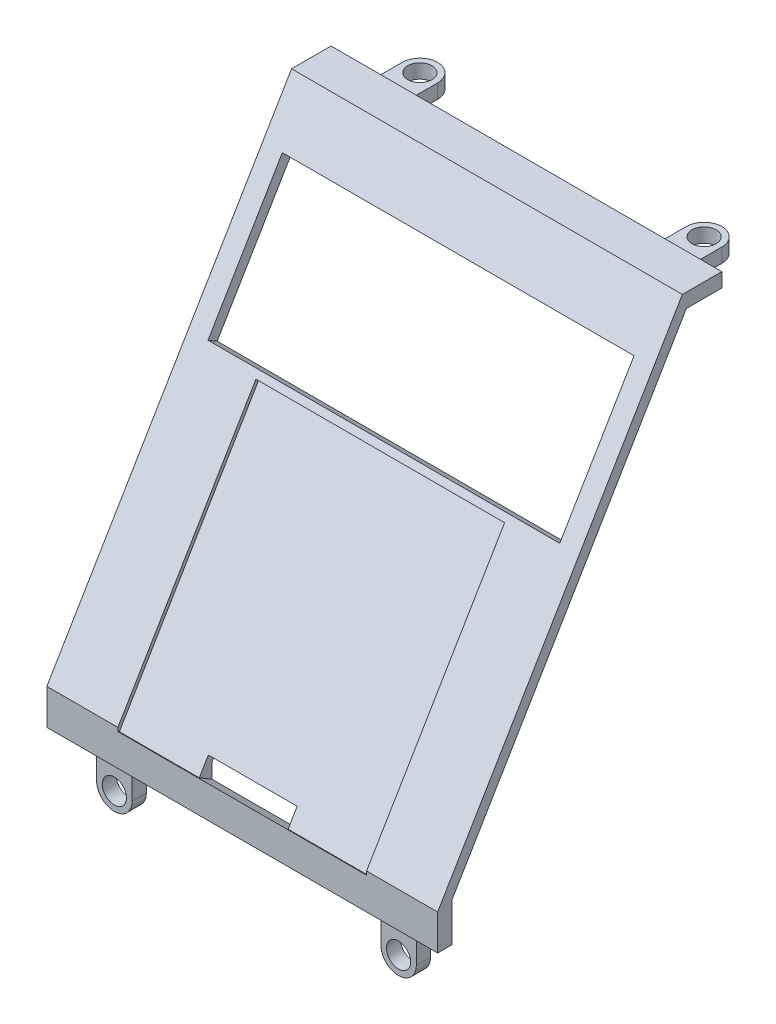
SolidWorks part; units mm, degrees
ref_plane "Front Plane" through (0, 0, 0) normal (0, 0, 1) x (1, 0, 0)
ref_plane "Top Plane" through (0, 0, 0) normal (0, 1, 0) x (1, 0, 0)
ref_plane "Right Plane" through (0, 0, 0) normal (1, 0, 0) x (0, 0, -1)
sketch "Sketch2" plane through (0, 0, 0) normal (1, 0, 0) x (0, 0, -1)
  line L0 (-52.1213, -63.9815) -> (16.7636, 52.1213)
  line L1 (16.7636, 52.1213) -> (27.8787, 52.1213)
  line L2 (27.8787, 52.1213) -> (27.8787, 48.1213)
  line L3 (27.8787, 48.1213) -> (17.8787, 48.1213)
  line L4 (17.8787, 48.1213) -> (-48.1213, -63.119)
  line L5 (-48.1213, -63.119) -> (-48.1213, -73.9815)
  line L6 (-48.1213, -73.9815) -> (-52.1213, -73.9815)
  line L7 (-52.1213, -73.9815) -> (-52.1213, -63.9815)
  line L9 (80.8787, 52.1213) -> (-52.1213, 52.1213) construction
  line L10 (-52.1213, -45.8787) -> (-52.1213, -96.8787) construction
  line L11 (27.8787, 148.1213) -> (27.8787, -96.8787) construction
  dimension "D1" = 135
  dimension "D2" = 3
  dimension "D3" = 4
  dimension "D4" = 4
  dimension "D5" = 10
  dimension "D6" = 10
extrude "Boss-Extrude1" add sketch "Sketch2" along normal mid plane 110
sketch "Sketch3" plane through (0, 6.2141, 10.4736) normal (0, 0.5103, 0.86) x (1, 0, 0)
  line L1 (-49.5, 37.5081) -> (49.5, 37.5081)
  line L2 (-49.5, 37.5081) -> (-49.5, -3.4919)
  line L3 (-49.5, -3.4919) -> (49.5, -3.4919)
  line L4 (49.5, 37.5081) -> (49.5, -3.4919)
  line L5 (55, 53.3792) -> (-55, 53.3792) construction
  point P9 (0, 37.5081)
  point P10 (0, 53.3792)
  dimension "D1" = 99
  dimension "D2" = 41
  dimension "D3" = 13
extrude "Cut-Extrude1" cut sketch "Sketch3" against normal up to next
sketch "Sketch4" plane through (0, 6.2141, 10.4736) normal (0, 0.5103, 0.86) x (1, 0, 0)
  line L0 (55, -81.6208) -> (-55, -81.6208) construction
  line L1 (-35, -5.4919) -> (35, -5.4919)
  line L2 (-35, -5.4919) -> (-35, -82.4919)
  line L3 (-35, -82.4919) -> (35, -82.4919)
  line L4 (35, -5.4919) -> (35, -82.4919)
  line L6 (-49.5, -3.4919) -> (49.5, -3.4919) construction
  point P4 (0, -82.4919)
  point P7 (0, -81.6208)
  dimension "D1" = 77
  dimension "D2" = 70
  dimension "D3" = 2
extrude "Cut-Extrude2" cut sketch "Sketch4" against normal blind 1
sketch "Sketch5" plane through (0, 4.6833, 7.8935) normal (0, -0.5103, -0.86) x (-1, 0, 0)
  line L0 (0, 40.1987) -> (0, -3.4919) construction
  line L1 (-49.5, -3.4919) -> (49.5, -3.4919) construction
  line L3 (-46.5, 44.4081) -> (-46.5, -10.3919) construction
  line L4 (-49.5, -3.4919) -> (-49.5, 37.5081) construction
  circle A0 centre (-46.5, 44.4081) radius 1.5
  circle A1 centre (-46.5, 44.4081) radius 4
  circle A2 centre (-46.5, -10.3919) radius 1.5
  circle A3 centre (-46.5, -10.3919) radius 4
  circle A4 centre (46.5, -10.3919) radius 4
  circle A5 centre (46.5, -10.3919) radius 1.5
  circle A6 centre (46.5, 44.4081) radius 4
  circle A7 centre (46.5, 44.4081) radius 1.5
  point P19 (-49.5, 17.0081)
  point P20 (-46.5, 17.0081)
  dimension "D3" = 3
  dimension "D4" = 8
  dimension "D1" = 54.8
  dimension "D2" = 93
extrude "Boss-Extrude2" add sketch "Sketch5" along normal blind 3
sketch "Sketch6" plane through (0, 0, -27.8787) normal (0, 0, -1) x (-1, 0, 0)
  line L0 (-55, 48.1213) -> (55, 48.1213) construction
  line L1 (45, 48.1213) -> (35, 48.1213)
  line L2 (45, 48.1213) -> (45, 44.1213)
  line L3 (45, 44.1213) -> (35, 44.1213)
  line L4 (35, 48.1213) -> (35, 44.1213)
  line L5 (-35, 44.1213) -> (-45, 44.1213)
  line L6 (-35, 44.1213) -> (-35, 48.1213)
  line L7 (-35, 48.1213) -> (-45, 48.1213)
  line L8 (-45, 44.1213) -> (-45, 48.1213)
  line L10 (-35, 48.1213) -> (35, 48.1213) construction
  point P10 (-35, 46.1213)
  point P11 (0, 48.1213)
  point P12 (0, 48.1213)
  dimension "D1" = 4
  dimension "D2" = 70
  dimension "D3" = 10
extrude "Boss-Extrude3" add sketch "Sketch6" along normal blind 15 and the other way up to next
sketch "Sketch7" plane through (0, 44.1213, 0) normal (0, -1, 0) x (1, 0, 0)
  line L0 (-35, -42.8787) -> (-45, -42.8787) construction
  line L1 (45, -42.8787) -> (35, -42.8787) construction
  circle A0 centre (-40, -37.8787) radius 3.41
  circle A1 centre (40, -37.8787) radius 3.41
  point P7 (-40, -42.8787)
  point P12 (40, -42.8787)
  dimension "D1" = 6.82
  dimension "D2" = 5
extrude "Cut-Extrude3" cut sketch "Sketch7" against normal up to next
fillet "Fillet1" radius 3 8 edges at (-35, 46.1213, -16.6921) (35, 46.1213, -16.6921) (45, 48.1213, -22.8787) (35, 48.1213, -22.8787) (38.8858, 44.1213, -15.5054) (-38.8858, 44.1213, -15.5054) (-45, 48.1213, -22.8787) (-35, 48.1213, -22.8787)
fillet "Fillet2" radius 5 4 edges at (45, 46.1213, -42.8787) (35, 46.1213, -42.8787) (-35, 46.1213, -42.8787) (-45, 46.1213, -42.8787)
sketch "Sketch8" plane through (0, 5.7038, 9.6136) normal (0, 0.5103, 0.86) x (1, 0, 0)
  line L0 (-35, -82.4919) -> (35, -82.4919) construction
  line L1 (-12.5, -77.4919) -> (12.5, -77.4919)
  line L2 (-12.5, -77.4919) -> (-12.5, -82.4919)
  line L3 (-12.5, -82.4919) -> (12.5, -82.4919)
  line L4 (12.5, -77.4919) -> (12.5, -82.4919)
  point P6 (0, -82.4919)
  point P7 (0, -77.4919)
  dimension "D1" = 25
  dimension "D2" = 5
extrude "Cut-Extrude4" cut sketch "Sketch8" against normal up to next
sketch "Sketch9" plane through (0, -73.9815, 0) normal (0, -1, 0) x (1, 0, 0)
  line L0 (55, 48.1213) -> (-55, 48.1213) construction
  line L1 (-45, 48.1213) -> (-35, 48.1213)
  line L2 (-45, 48.1213) -> (-45, 44.1213)
  line L3 (-45, 44.1213) -> (-35, 44.1213)
  line L4 (-35, 48.1213) -> (-35, 44.1213)
  line L5 (0, 56.2428) -> (0, 40.7977) construction
  line L8 (-55, 52.1213) -> (-55, 48.1213) construction
  line L9 (35, 48.1213) -> (35, 44.1213)
  line L10 (45, 44.1213) -> (35, 44.1213)
  line L11 (45, 48.1213) -> (45, 44.1213)
  line L12 (45, 48.1213) -> (35, 48.1213)
  dimension "D1" = 4
  dimension "D2" = 10
  dimension "D3" = 10
extrude "Boss-Extrude4" add sketch "Sketch9" along normal blind 15 and the other way up to next
sketch "Sketch10" plane through (0, 0, 44.1213) normal (0, 0, -1) x (-1, 0, 0)
  line L6 (0, -91.495) -> (0, -68.9649) construction
  line L10 (45, -88.9815) -> (35, -88.9815) construction
  circle A1 centre (40, -83.9815) radius 3.41
  circle A2 centre (-40, -83.9815) radius 3.41
  point P4 (40, -88.9815)
  dimension "D1" = 6.82
  dimension "D2" = 5
extrude "Cut-Extrude5" cut sketch "Sketch10" against normal up to next
fillet "Fillet3" radius 3 10 edges at (35, -59.7481, 46.1213) (45, -59.7481, 46.1213) (-35, -59.7481, 46.1213) (-45, -59.7481, 46.1213) (-45, -68.5503, 48.1213) (-40, -56.3772, 44.1213) (-35, -68.5503, 48.1213) (45, -68.5503, 48.1213) (40, -56.3772, 44.1213) (35, -68.5503, 48.1213)
fillet "Fillet4" radius 5 4 edges at (-45, -88.9815, 46.1213) (-35, -88.9815, 46.1213) (35, -88.9815, 46.1213) (45, -88.9815, 46.1213)
equation "\"Printed Hole Size\"= 6.5"
equation "\"CAD Hole Size\"= 0.9683 * \"Printed Hole Size\" + 0.5265"
